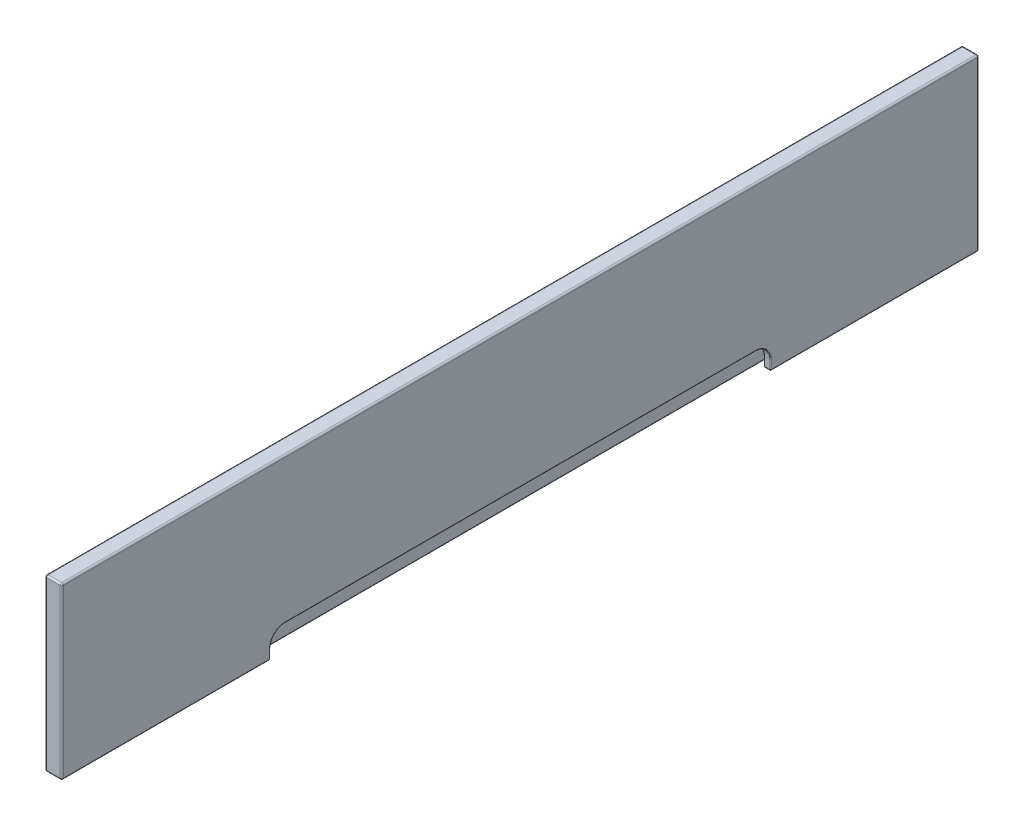
SolidWorks part; units mm, degrees
ref_plane "Front Plane" through (0, 0, 0) normal (0, 0, 1) x (1, 0, 0)
ref_plane "Top Plane" through (0, 0, 0) normal (0, 1, 0) x (1, 0, 0)
ref_plane "Right Plane" through (0, 0, 0) normal (1, 0, 0) x (0, 0, -1)
sketch "Sketch1" plane through (0, 0, 0) normal (1, 0, 0) x (0, 0, -1)
  line L1 (550, -102) -> (-550, -102)
  line L2 (550, -102) -> (550, 102)
  line L3 (550, 102) -> (-550, 102)
  line L4 (-550, -102) -> (-550, 102)
  line L5 (550, -102) -> (-550, 102) construction
  line L6 (550, 102) -> (-550, -102) construction
  point P0 (0, 0)
  dimension "D1" = 1100
  dimension "D2" = 204
extrude "Boss-Extrude1" add sketch "Sketch1" against normal blind 20
sketch "Sketch3" plane through (0, 0, 0) normal (1, 0, 0) x (0, 0, -1)
  line L0 (-550, -102) -> (550, -102) construction
  line L1 (-300, -102) -> (300, -102)
  line L2 (-300, -102) -> (-300, -90)
  line L3 (-282, -72) -> (282, -72)
  line L4 (300, -102) -> (300, -90)
  arc A0 (282, -72) -> (300, -90) centre (282, -90) cw
  arc A1 (-300, -90) -> (-282, -72) centre (-282, -90) cw
  point P4 (0, -102)
  point P10 (300, -72)
  point P13 (-300, -72)
  dimension "D3" = 18
  dimension "D1" = 30
  dimension "D2" = 600
extrude "Cut-Extrude2" cut sketch "Sketch3" against normal blind 15
sketch "Sketch4" plane through (-15, 0, 0) normal (1, 0, 0) x (0, 0, -1)
  line L0 (-300, -102) -> (300, -102) construction
  line L1 (-320, -102) -> (320, -102)
  line L2 (-320, -102) -> (-320, -85)
  line L3 (-297, -62) -> (297, -62)
  line L4 (320, -102) -> (320, -85)
  arc A0 (297, -62) -> (320, -85) centre (297, -85) cw
  arc A1 (-320, -85) -> (-297, -62) centre (-297, -85) cw
  point P6 (0, -62)
  point P10 (320, -62)
  point P13 (-320, -62)
  dimension "D3" = 23
  dimension "D1" = 640
  dimension "D2" = 40
extrude "Cut-Extrude3" cut sketch "Sketch4" along normal blind 7
fillet "Fillet1" radius 1 20 edges at (-8, -93.5, -320) (-8, -68.7365, -313.2635) (-8, -62, 0) (-8, -93.5, 320) (0, -96, -300) (0, -77.2721, -294.7279) (0, -96, 300) (0, -77.2721, 294.7279) (-8, -96, -300) (-8, -77.2721, -294.7279) (-8, -96, 300) (-8, -77.2721, 294.7279) (-15, -93.5, -320) (-15, -68.7365, -313.2635) (-15, -93.5, 320) (-15, -68.7365, 313.2635) (-8, -68.7365, 313.2635) (0, -72, 0) (-8, -72, 0) (-15, -62, 0)
fillet "Fillet2" radius 2 28 edges at (-10, -102, -550) (-0.2929, -102, 300.2929) (-4, -102, 300) (-7.7071, -102, 300.2929) (-8, -102, 310) (-8.2929, -102, 319.7071) (-11.5, -102, 320) (-14.7071, -102, 319.7071) (-15, -102, 0) (-14.7071, -102, -319.7071) (-11.5, -102, -320) (-8.2929, -102, -319.7071) (-8, -102, -310) (-7.7071, -102, -300.2929) (-4, -102, -300) (-0.2929, -102, -300.2929) (-10, -102, 550) (-20, -102, 0) (-20, 0, -550) (-20, 0, 550) (-10, 102, 550) (-20, 102, 0) (-10, 102, -550) (0, -102, 425.5) (0, 0, 550) (0, 102, 0) (0, 0, -550) (0, -102, -425.5)
